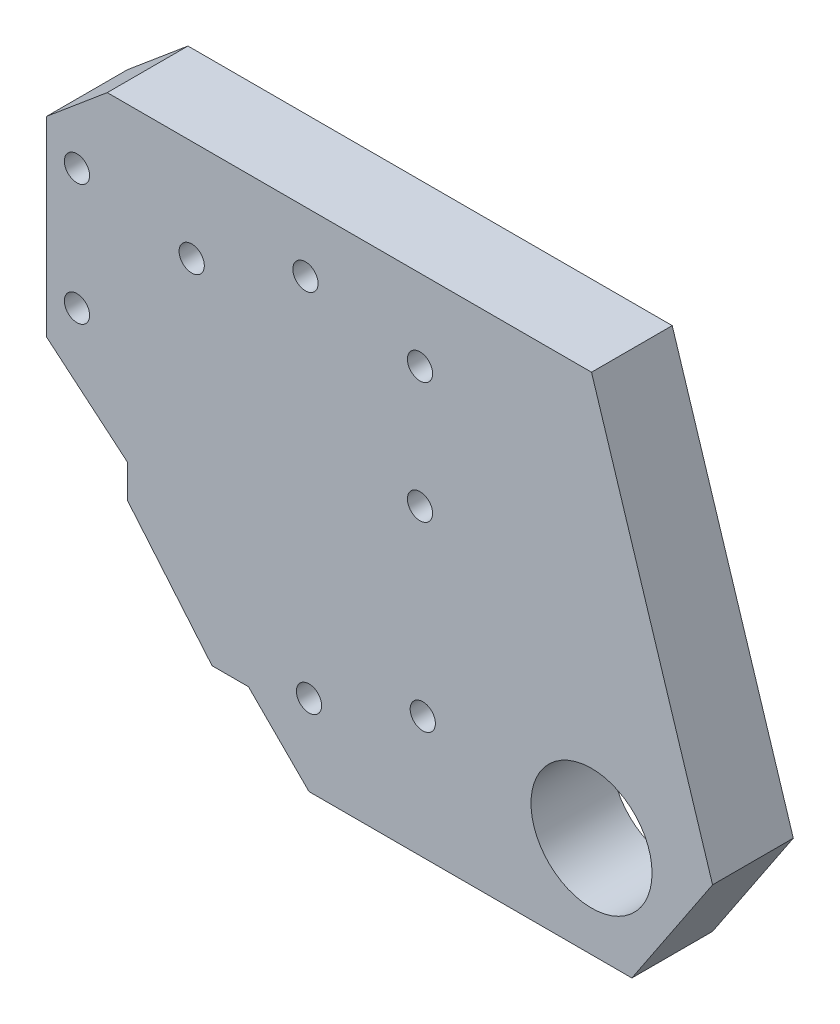
SolidWorks part; units mm, degrees
material "6061 合金"
ref_plane "前视基准面" through (0, 0, 0) normal (0, 0, 1) x (1, 0, 0)
ref_plane "上视基准面" through (0, 0, 0) normal (0, 1, 0) x (1, 0, 0)
ref_plane "右视基准面" through (0, 0, 0) normal (1, 0, 0) x (0, 0, -1)
sketch "草图1" plane through (0, 0, 0) normal (0, 0, 1) x (1, 0, 0)
  line L0 (0, 3) -> (0, 13)
  line L2 (23, 25) -> (29, 6)
  line L3 (29, 6) -> (25, 0)
  line L4 (25, 0) -> (9, 0)
  line L5 (23, 25) -> (-4, 25)
  line L6 (-4, 25) -> (-4, 13)
  line L7 (-4, 13) -> (0, 13)
  line L9 (0, 3) -> (6, 3)
  line L10 (6, 3) -> (9, 0)
  line L11 (0, 0) -> (0, 3) construction
  line L12 (9, 0) -> (0, 0) construction
  circle A0 centre (23, 5) radius 3
  dimension "D6" = 6
  dimension "D2" = 6
  dimension "D3" = 25
  dimension "D4" = 27
  dimension "D5" = 4
  dimension "D7" = 6
  dimension "D8" = 5
  dimension "D9" = 4
  dimension "D10" = 25
  dimension "D11" = 12
  dimension "D12" = 3
  dimension "D13" = 3
  dimension "D14" = 6
extrude "凸台-拉伸1" add sketch "草图1" along normal blind 4
hole_wizard "M1.6 螺纹孔1" positions "草图3" profile "草图2" tap size "M1.6" standard "Gb"
sketch "草图3" plane through (0, 0, 4) normal (0, 0, 1) x (1, 0, 0)
  line L0 (-2.5, 21) -> (14.5, 21) construction
  line L1 (14.5, 21) -> (14.5, 15) construction
  line L2 (14.5, 15) -> (-2.5, 15) construction
  line L3 (-2.5, 15) -> (-2.5, 21) construction
  line L6 (23, 25) -> (-4, 25) construction
  line L7 (-4, 25) -> (-4, 13) construction
  point P1 (-2.5, 21)
  point P2 (14.5, 21)
  point P4 (14.5, 15)
  point P6 (-2.5, 15)
  dimension "D1" = 6
  dimension "D2" = 17
  dimension "D3" = 1.5
  dimension "D4" = 4
sketch "草图2" plane through (-2.5, 21, 4) normal (1, 0, 0) x (0, -1, 0)
  line L0 (0, 0) -> (0, 5.3255)
  line L1 (0, 5.3255) -> (0.625, 4.95)
  line L2 (0.625, 4.95) -> (0.625, 0)
  line L5 (0.625, 0) -> (0, 0)
  line L10 (0, 5.3255) -> (-0.625, 4.95) construction
  line L11 (0, -6.35) -> (0, 107.95) construction
  dimension "螺纹孔钻头直径" = 1.25
  dimension "螺纹孔钻头深度" = 4.95
  dimension "导头角度" = 118
cosmetic thread "孔螺蚊线1" parameters "D1"=3, "D2"=1.6
cosmetic thread "孔螺蚊线2" parameters "D1"=3, "D2"=1.6
cosmetic thread "孔螺蚊线4" parameters "D1"=3, "D2"=1.6
cosmetic thread "孔螺蚊线5" parameters "D1"=3, "D2"=1.6
hole_wizard "M1.6 螺纹孔2" positions "草图5" profile "草图4" tap size "M1.6" standard "Gb"
sketch "草图5" plane through (0, 0, 4) normal (0, 0, 1) x (1, 0, 0)
  line L0 (8.8238, 22.0269) -> (14.6382, 6.0521) construction
  line L1 (14.6382, 6.0521) -> (9, 4) construction
  line L2 (9, 4) -> (3.1857, 19.9748) construction
  line L3 (3.1857, 19.9748) -> (8.8238, 22.0269) construction
  line L4 (9, 0) -> (25, 0) construction
  line L5 (0, 13) -> (0, 3) construction
  point P1 (8.8238, 22.0269)
  point P2 (14.6382, 6.0521)
  point P4 (9, 4)
  point P6 (3.1857, 19.9748)
  dimension "D1" = 17
  dimension "D2" = 6
  dimension "D3" = 70
  dimension "D4" = 4
  dimension "D5" = 9
sketch "草图4" plane through (8.8238, 22.0269, 4) normal (1, 0, 0) x (0, -1, 0)
  line L0 (0, 0) -> (0, 5.3255)
  line L1 (0, 5.3255) -> (0.625, 4.95)
  line L2 (0.625, 4.95) -> (0.625, 0)
  line L5 (0.625, 0) -> (0, 0)
  line L10 (0, 5.3255) -> (-0.625, 4.95) construction
  line L11 (0, -6.35) -> (0, 107.95) construction
  dimension "螺纹孔钻头直径" = 1.25
  dimension "螺纹孔钻头深度" = 4.95
  dimension "导头角度" = 118
cosmetic thread "孔螺蚊线6" parameters "D1"=3, "D2"=1.6
cosmetic thread "孔螺蚊线7" parameters "D1"=3, "D2"=1.6
cosmetic thread "孔螺蚊线8" parameters "D1"=3, "D2"=1.6
cosmetic thread "孔螺蚊线9" parameters "D1"=3, "D2"=1.6
chamfer "倒角1" distance 5 angle 40 1 edges at (0, 3, 2) first distance on face at (0, 8, 2)
chamfer "倒角2" distance 4 angle 40 1 edges at (0, 13, 2) first distance on face at (-2, 13, 2)
chamfer "倒角4" distance 3 angle 40 1 edges at (-4, 25, 2) first distance on face at (9.5, 25, 2)
